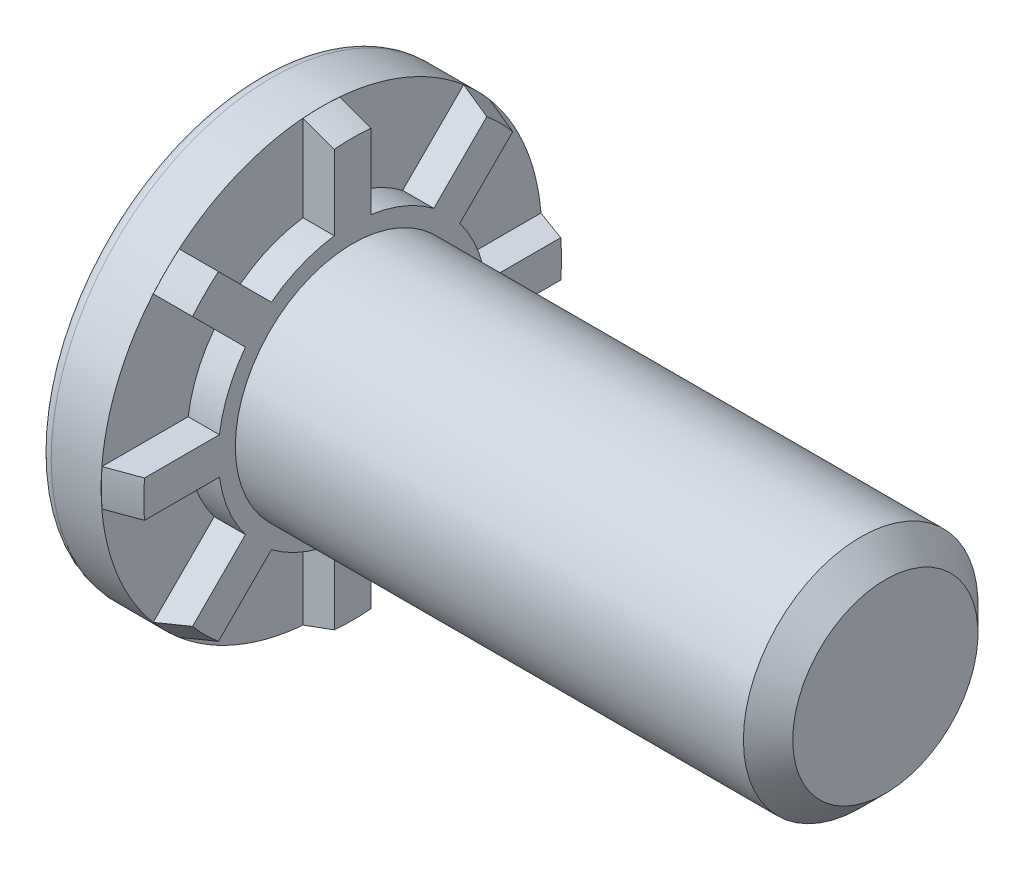
SolidWorks part; units mm, degrees
revolve "BaseBody" add sketch "BodySke" angle 360 about L6 other way angle 7.5
sketch "BodySke" plane through (0, 0, 0) normal (0, 0, 1) x (1, 0, 0)
  line L0 (-2.1082, 7.0206) -> (-2.1082, 0)
  line L1 (1.0541, 7.0569) -> (1.0541, 3.9624)
  line L2 (0.0025, 7.4397) -> (1.0541, 7.0569)
  line L3 (1.0541, 3.9624) -> (18.2169, 3.9624)
  line L4 (19.05, 3.1293) -> (19.05, 0)
  line L5 (19.05, 0) -> (-2.1082, 0)
  line L6 (0, 0) -> (50.554, 0) construction
  line L8 (19.05, 3.1293) -> (18.2169, 3.9624)
  line L9 (-1.6866, 7.4422) -> (0, 7.4422)
  line L10 (0.0025, 7.4397) -> (0, 7.4397)
  line L11 (1.4097, 19.05) -> (1.4097, -3.175) construction
  line L12 (0, 7.4397) -> (0, 7.4422)
  arc A0 (-2.1082, 7.0206) -> (-1.6866, 7.4422) centre (-1.6866, 7.0206) cw
  dimension "Fillet_rad" = 0.4216
  dimension "Minor_dia" = 6.2586
  dimension "Diameter" = 7.9248
  dimension "T_dim" = 2.1082
  dimension "H_dia" = 14.8844
  dimension "D2" = 0.0025
  dimension "D3" = 0.0025
  dimension "Length" = 19.05
  dimension "Advance" = 1.4097
  dimension "D1" = 20
cosmetic thread "ThreadCosmetic" [suppressed] parameters "Thread_length"=15.6718, "Thread_minor"=6.2586
ref_plane "Plane1" through (0, 0, 0) normal (0, 0, 1) x (1, 0, 0)
ref_plane "Plane2" through (0, 0, 0) normal (0, 1, 0) x (1, 0, 0)
ref_plane "Plane3" through (0, 0, 0) normal (1, 0, 0) x (0, 0, -1)
sketch "ThdSchSke" plane through (0, 0, 0) normal (0, 0, 1) x (1, 0, 0)
  line L0 (3.3782, -3.1293) -> (2.7948, -3.9624)
  line L1 (3.3782, -3.1293) -> (3.9616, -3.9624)
  line L2 (3.9616, -3.9624) -> (3.9616, -4.953)
  line L3 (-3.175, 0) -> (5.1513, 0) construction
  line L4 (0, -7.4422) -> (0, 7.4422) construction
  line L5 (3.9616, -4.953) -> (2.7948, -4.953)
  line L6 (2.7948, -4.953) -> (2.7948, -3.9624)
  dimension "Diameter" = 7.9248
  dimension "Thread_minor" = 6.2586
  dimension "Start" = 3.3782
revolve "ThreadSchematic" [suppressed] cut sketch "ThdSchSke" angle 360 about L3
pattern_linear "ThdSchPat" [suppressed]
sketch "RibCutSke" plane through (1.0541, 1.7944, -0.091) normal (1, 0, 0) x (0, 0, -1)
  line L0 (0.5289, 2.7055) -> (0.5289, 5.6219)
  line L1 (2.6526, 1.8258) -> (4.7149, 3.888)
  line L2 (0.5289, 2.1192) -> (0.5289, 2.4006) construction
  line L3 (-0.091, -1.7944) -> (-0.091, 5.0239) construction
  line L4 (-0.091, -1.7944) -> (0.5289, 2.1192) construction
  line L5 (-0.091, -1.7944) -> (2.2381, 1.4112) construction
  line L6 (2.2381, 1.4112) -> (2.4421, 1.6153) construction
  arc A1 (2.6526, 1.8258) -> (0.5289, 2.7055) centre (-0.091, -1.7944) ccw
  arc A2 (4.7149, 3.888) -> (0.5289, 5.6219) centre (-0.091, -1.7944) ccw
  circle A3 centre (-0.091, -1.7944) radius 7.0569 construction
  circle A4 centre (-0.091, -1.7944) radius 3.9624 construction
  dimension "Rib_root_half_angle" = 9
  dimension "Rib_root_gap_angle" = 27
  dimension "Angle" = 45
extrude "RibCut" cut sketch "RibCutSke" against normal blind 1.0541
pattern_circular "RibCutsPat" count 8 every 45 about axis through (0, 0, 0) along (1, 0, 0) of "RibCut"
equation "' \"Length@BodySke\" = 0.75"
equation "' \"H_dia@BodySke\" = 0.586"
equation "' \"Start@ThdSchSke\" = 0.133"
equation "' \"T_dim@BodySke\" = 0.083"
equation "' \"Diameter@BodySke\" = 0.312"
equation "' \"Minor_dia@BodySke\" = 0.2464"
equation "' \"Advance@BodySke\" = 0.0555"
equation "\"Fillet_rad@BodySke\" =  \"T_dim@BodySke\" * 0.2"
equation "\"Clinch_ht@BodySke\" = \"T_dim@BodySke\" * 0.5"
equation "\"Num_ribs@RibCutsPat\" = 8"
equation "\"Angle@RibCutSke\" =\"Angle@RibCutsPat\""
equation "\"Rib_root_half_angle@RibCutSke\" = \"Angle@RibCutSke\" / 5"
equation "\"Rib_root_gap_angle@RibCutSke\" = \"Angle@RibCutSke\" - (2 * \"Rib_root_half_angle@RibCutSke\" )"
equation "\"Rib_root_dia@RibCutSke\" = \"Diameter@BodySke\""
equation "\"Inner_dia@RibCutSke\" = \"Diameter@BodySke\" + ( \"H_dia@BodySke\" - \"Diameter@BodySke\" ) / 6"
equation "\"Outer_dia@RibCutSke\" = \"H_dia@BodySke\""
equation "\"Depth@RibCut\" = \"Clinch_ht@BodySke\""
equation "\"Thread_length@ThreadCosmetic\" = \"Length@BodySke\" - \"Start@ThdSchSke\""
equation "\"Thread_minor@ThreadCosmetic\" = \"Minor_dia@BodySke\""
equation "\"Thread_minor@ThdSchSke\" = \"Minor_dia@BodySke\""
equation "\"Diameter@ThdSchSke\" = \"Diameter@BodySke\""
equation "\"Overcut@ThdSchSke\" = \"Diameter@BodySke\" * 1.25"
equation "\"Num_threads@ThdSchPat\" = int( \"Thread_length@ThreadCosmetic\" / \"Advance@BodySke\" + 0.999 )  + 1"
equation "\"Advance@ThdSchPat\" = \"Thread_length@ThreadCosmetic\" /  (\"Num_threads@ThdSchPat\" - 1) 'relax it"
equation "\"Num_threads@ThdSchPat\" = \"Num_threads@ThdSchPat\" - sgn( \"Num_threads@ThdSchPat\" - 1) '---chamfered tips only---"
